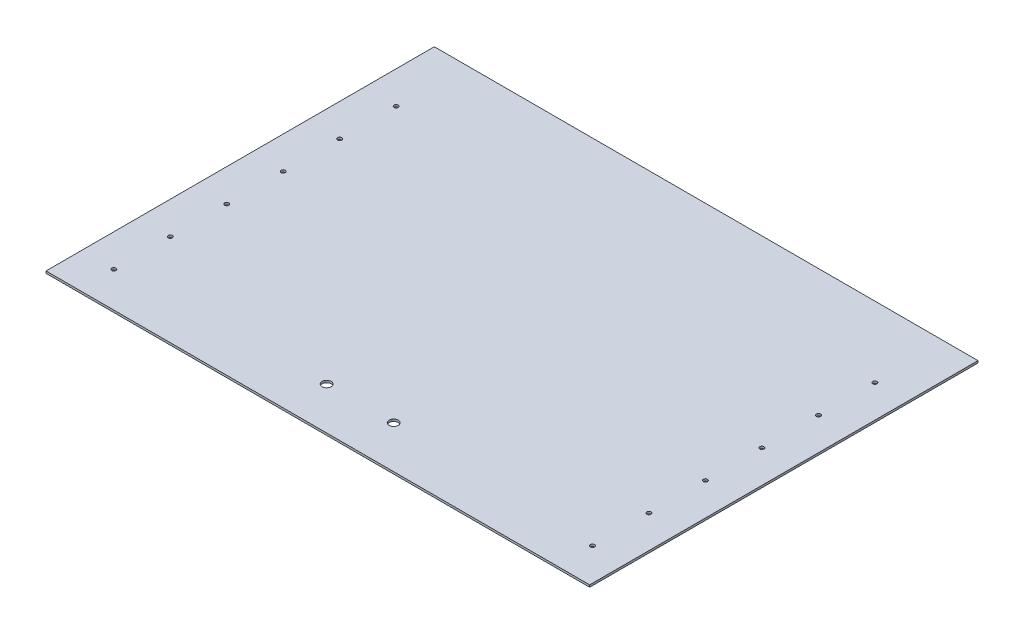
SolidWorks part; units mm, degrees
ref_plane "Front Plane" through (0, 0, 0) normal (0, 0, 1) x (1, 0, 0)
ref_plane "Top Plane" through (0, 0, 0) normal (0, 1, 0) x (1, 0, 0)
ref_plane "Right Plane" through (0, 0, 0) normal (1, 0, 0) x (0, 0, -1)
sketch "Sketch1" plane through (0, 0, 0) normal (0, 1, 0) x (1, 0, 0)
  line L0 (0, 275) -> (0, -275) construction
  line L1 (-385, 275) -> (385, 275)
  line L2 (-385, 275) -> (-385, -275)
  line L3 (-385, -275) -> (385, -275)
  line L4 (385, 275) -> (385, -275)
  line L5 (-385, 275) -> (385, -275) construction
  line L6 (-385, -275) -> (385, 275) construction
  circle A0 centre (-339, 175) radius 3
  circle A1 centre (-339, 95) radius 3
  circle A2 centre (-339, 15) radius 3
  circle A3 centre (-339, -65) radius 3
  circle A4 centre (-339, -145) radius 3
  circle A5 centre (-339, -225) radius 3
  circle A8 centre (339, -225) radius 3
  circle A9 centre (339, -145) radius 3
  circle A10 centre (339, -65) radius 3
  circle A11 centre (339, 15) radius 3
  circle A12 centre (339, 95) radius 3
  circle A13 centre (339, 175) radius 3
  circle A14 centre (-339, -305) radius 3
  circle A15 centre (-47.5, -215) radius 6.5
  circle A16 centre (47.5, -215) radius 6.5
  point P0 (0, 0)
  dimension "D5" = 6
  dimension "D7" = 13
  dimension "D1" = 550
  dimension "D2" = 770
  dimension "D3" = 339
  dimension "D4" = 100
  dimension "D8" = 47.5
  dimension "D9" = 60
  dimension "D6" = 7
base flange "Base-Flange1" sketch "Sketch1" thickness 3 reverse thickness direction no parameters "D1"=0.7366
sketch "Bend-Lines1" [suppressed] plane through (0, 0, 0) normal (0, 1, 0) x (1, 0, 0)
sketch "Bounding-Box1" [suppressed] plane through (0, 0, 0) normal (0, 1, 0) x (1, 0, 0)
sheet metal parameters "Sheet-Metal1" thickness 3 parameters "D1"=0.7366
flat pattern "Flat-Pattern1" [suppressed]
sketch "Bend-Lines2" plane through (0, 0, 0) normal (0, 1, 0) x (1, 0, 0)
sketch3d "Bounding-Box2" [suppressed]
  line L0 (385, -275, 0) -> (-385, -275, 0) construction
  line L1 (385, 275, 0) -> (-385, 275, 0) construction
  line L2 (385, -275, 0) -> (385, 275, 0) construction
  line L3 (-385, -275, 0) -> (-385, 275, 0) construction
